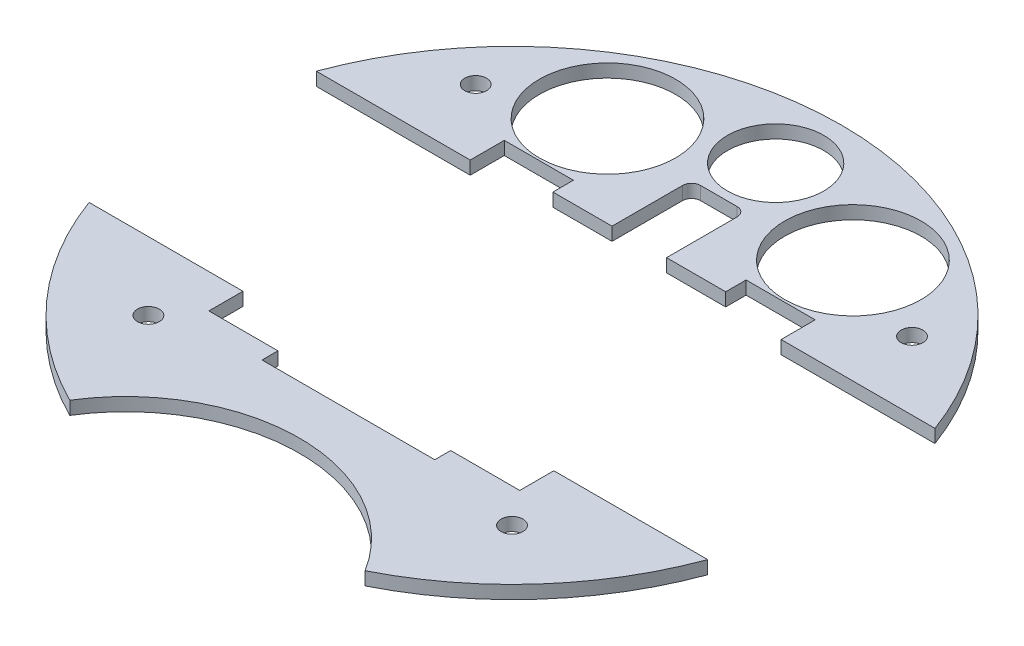
SolidWorks part; units mm, degrees
material "ABS"
ref_plane "Front Plane" through (0, 0, 0) normal (0, 0, 1) x (1, 0, 0)
ref_plane "Top Plane" through (0, 0, 0) normal (0, 1, 0) x (1, 0, 0)
ref_plane "Right Plane" through (0, 0, 0) normal (1, 0, 0) x (0, 0, -1)
sketch "Sketch1" plane through (0, 0, 0) normal (0, 1, 0) x (1, 0, 0)
  line L0 (0, -85) -> (-32.4891, -64.8129) construction
  line L1 (0, -85) -> (0, 0) construction
  arc A0 (32.4891, -64.8129) -> (-32.4891, -64.8129) centre (0, 0) ccw
  arc A1 (32.4891, -64.8129) -> (-32.4891, -64.8129) centre (0, -85) ccw
  dimension "D1" = 145
  dimension "D2" = 76.5
  dimension "D3" = 85
extrude "Boss-Extrude1" add sketch "Sketch1" along normal blind 2.9
sketch "solenoid placement" plane through (0, 2.9, 0) normal (0, 1, 0) x (1, 0, 0)
  line L4 (-19, -36) -> (19, -36)
  line L5 (-19, 28) -> (-19, -36)
  line L10 (19, 28) -> (-19, 28)
  line L11 (19, -36) -> (19, 28)
  line L12 (-19, -36) -> (19, -36)
  line L13 (-19, 28) -> (-19, -36)
  line L14 (19, 28) -> (-19, 28)
  line L15 (19, -36) -> (19, 28)
  dimension "D1" = 0
extrude "Cut-Extrude1" cut sketch "solenoid placement" against normal through all
sketch "Sketch7" plane through (0, 2.9, 0) normal (0, 1, 0) x (1, 0, 0)
  circle A3 centre (27, 48) radius 15
  circle A4 centre (27, 48) radius 15
  circle A5 centre (-27, 48) radius 15
  circle A6 centre (-27, 48) radius 15
  dimension "D1" = 0
  dimension "D2" = 0
extrude "Cut-Extrude6" cut sketch "Sketch7" against normal through all
sketch "Sketch8" plane through (0, 2.9, 0) normal (0, 1, 0) x (1, 0, 0)
  circle A1 centre (40, -40) radius 2.4
  circle A2 centre (40, -40) radius 2.4
  circle A3 centre (-40, -40) radius 2.4
  circle A4 centre (-40, -40) radius 2.4
  circle A5 centre (48, 40) radius 2.4
  circle A6 centre (48, 40) radius 2.4
  circle A7 centre (-48, 40) radius 2.4
  circle A8 centre (-48, 40) radius 2.4
  dimension "D1" = 0
  dimension "D2" = 0
  dimension "D3" = 0
  dimension "D4" = 0
extrude "Cut-Extrude7" cut sketch "Sketch8" against normal through all
sketch "Sketch3" plane through (0, 2.9, 0) normal (0, 1, 0) x (1, 0, 0)
  line L1 (-34.2, -32.5) -> (-22.2, -32.5)
  line L2 (-34.2, 25) -> (-68.0533, 25)
  line L3 (-34.2, 32.5) -> (-22.2, 32.5)
  line L4 (-22.2, -32.5) -> (-22.2, 32.5) construction
  line L8 (0, 0) -> (0, 72.5) construction
  line L17 (-34.2, -32.5) -> (-34.2, -25)
  line L18 (-34.2, -25) -> (-68.0533, -25)
  line L19 (-34.2, 25) -> (-34.2, 32.5)
  line L21 (-22.2, 32.5) -> (-19, 32.5)
  line L22 (-22.2, 32.5) -> (-22.2, -32.5) construction
  line L23 (-22.2, -32.5) -> (-19, -32.5)
  line L24 (-19, 32.5) -> (-19, -32.5)
  line L25 (22.2, 32.5) -> (22.2, -32.5) construction
  line L26 (22.2, -32.5) -> (22.2, 32.5) construction
  line L27 (19, 32.5) -> (19, -32.5)
  line L28 (22.2, -32.5) -> (19, -32.5)
  line L29 (22.2, 32.5) -> (19, 32.5)
  line L30 (34.2, 25) -> (34.2, 32.5)
  line L31 (34.2, -25) -> (68.0533, -25)
  line L32 (34.2, -32.5) -> (34.2, -25)
  line L33 (34.2, 32.5) -> (22.2, 32.5)
  line L34 (34.2, 25) -> (68.0533, 25)
  line L35 (34.2, -32.5) -> (22.2, -32.5)
  line L36 (-19, 28) -> (-19, -36) construction
  arc A0 (32.4891, -64.8129) -> (-32.4891, -64.8129) centre (0, 0) ccw construction
  arc A2 (68.0533, 25) -> (68.0533, -25) centre (0, 0) cw
  arc A3 (-68.0533, 25) -> (-68.0533, -25) centre (0, 0) ccw
  point P31 (-34.2, -32.5)
  dimension "D1" = 50
extrude "Cut-Extrude3" cut sketch "Sketch3" against normal through all
sketch "Sketch9" plane through (0, 2.9, 0) normal (0, 1, 0) x (1, 0, 0)
  line L0 (6, 43.5) -> (6, 28)
  line L1 (-6, 43.5) -> (-6, 28)
  line L2 (19, 28) -> (-19, 28) construction
  line L8 (-6, 28) -> (6, 28)
  line L10 (4, 45.5) -> (-4, 45.5)
  arc A0 (-6, 43.5) -> (-4, 45.5) centre (-4, 43.5) cw
  arc A1 (6, 43.5) -> (4, 45.5) centre (4, 43.5) ccw
  point P5 (0, 28)
  point P6 (0, 28)
  point P16 (-6, 45.5)
  point P19 (6, 45.5)
  dimension "D3" = 2
  dimension "D2" = 12
  dimension "D1" = 17.5
extrude "Cut-Extrude8" cut sketch "Sketch9" against normal through all
sketch "Sketch10" plane through (0, 2.9, 0) normal (0, 1, 0) x (1, 0, 0)
  line L0 (0, 0) -> (0, 58) construction
  circle A0 centre (0, 58) radius 10.605
  point P6 (-8.8855, -65.4049)
  dimension "D1" = 21.21
  dimension "D2" = 58
extrude "Cut-Extrude9" cut sketch "Sketch10" against normal through all
equation "\"smallPulleyTeeth\"= 15"
equation "\"largePulleyTeeth\"= 30"
equation "\"eighthThick\"= 2.9mm"
equation "\"sixteenthThick\" = 1.7mm"
equation "\"quarterThick\"=6.0mm"
equation "\"OD\" = 145mm"
equation "\"puckAngle\" = 60.5deg"
equation "\"D1@Sketch1\"=\"OD\""
equation "\"puckDiam\" = 76.5mm"
equation "\"D2@Sketch1\"=\"puckDiam\""
equation "\"D1@Boss-Extrude1\"=\"eighthThick\""
equation "\"axlePress\" = 5.9mm"
equation "\"press\" = 0.2mm"
equation "\"wheelClear\" = 0.3mm"
equation "\"10-32clear\" = 4.8mm"
equation "\"6-32clear\" = 3.3mm"
equation "\"8-32clear\" = 4.0mm"
equation "\"4-40clear\" = 3.0mm"
equation "\"wheelHeight\" = 22mm"
equation "\"wheelWell\" = 65mm"
equation "\"puckDist\" = 85mm"
equation "\"D3@Sketch1\"=\"puckDist\""
equation "\"scoopFillet\" = 5mm"
